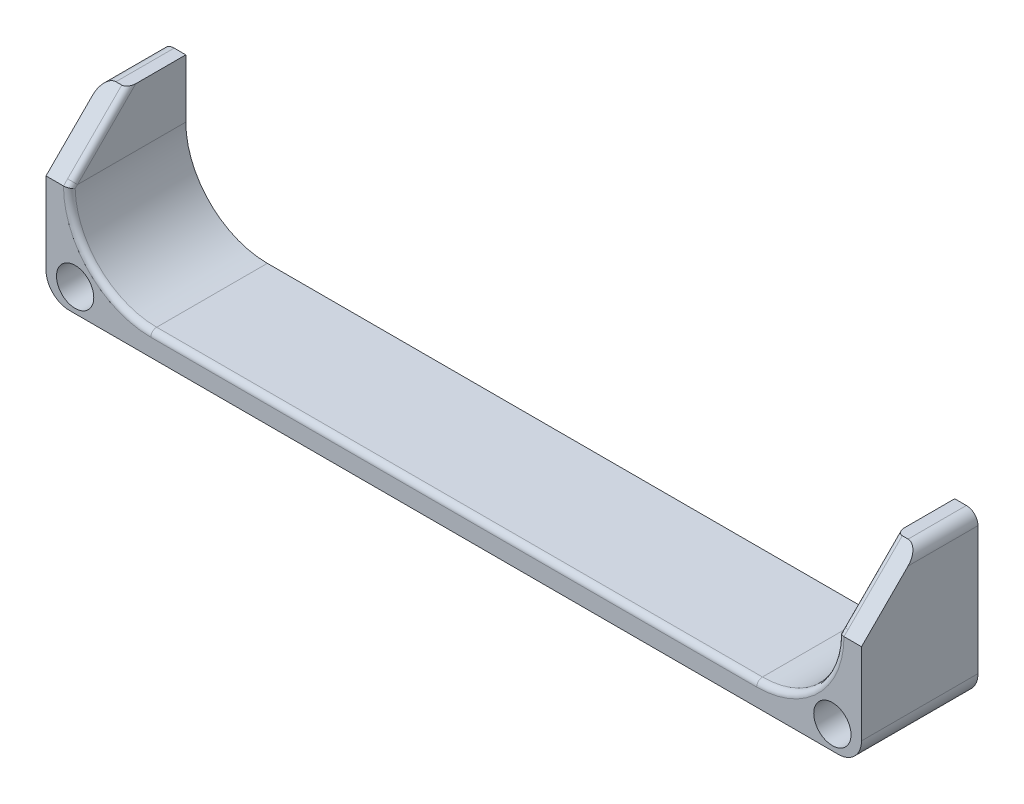
SolidWorks part; units mm, degrees
material "ABS"
ref_plane "Front" through (0, 0, 0) normal (0, 0, 1) x (1, 0, 0)
ref_plane "Top" through (0, 0, 0) normal (0, 1, 0) x (1, 0, 0)
ref_plane "Right" through (0, 0, 0) normal (1, 0, 0) x (0, 0, -1)
sketch "Croquis1" plane through (0, 0, 0) normal (0, 0, 1) x (1, 0, 0)
  line L0 (0, 0) -> (-70, 0)
  line L1 (-70, 0) -> (-70, 28)
  line L2 (-70, 28) -> (-66, 28)
  line L3 (-66, 28) -> (-66, 4)
  line L4 (-66, 4) -> (0, 4)
  line L5 (0, 4) -> (0, 0)
  line L6 (0, 4) -> (0, 31.2012) construction
  dimension "D1" = 140
  dimension "D2" = 4
  dimension "D3" = 4
  dimension "D4" = 28
extrude "Saliente-Extruir1" add sketch "Croquis1" along normal blind 20
fillet "Redondeo1" radius 14 1 edges at (-66, 4, 10)
fillet "Redondeo2" radius 4 1 edges at (-70, 0, 10)
chamfer "Chaflán1" distance 10 angle 45 1 edges at (-68, 28, 20)
sketch "Croquis3" plane through (0, 0, 0) normal (0, 0, 1) x (1, 0, 0)
  line L0 (0, 0) -> (0, 8.7858) construction
  line L1 (-66, 0) -> (0, 0) construction
  circle A0 centre (-65, 4) radius 1.8
  dimension "D1" = 130
  dimension "D2" = 4
  dimension "D3" = 3.6
extrude "Cortar-Extruir1" cut sketch "Croquis3" along normal through all
sketch "Croquis4" plane through (0, 0, 20) normal (0, 0, 1) x (1, 0, 0)
  circle A0 centre (-65, 4) radius 3.2
  dimension "D1" = 6.4
extrude "Cortar-Extruir2" cut sketch "Croquis4" against normal offset from surface (14 mm away) 6 up to face at (-63.2, 4, 0)
fillet "Redondeo3" radius 1 3 edges at (-66, 23, 15) (-61.8995, 8.1005, 20) (-26, 4, 20)
fillet "Redondeo4" radius 2 1 edges at (-70, 28, 5)
mirror "Simetría1" about plane through (0, 4, 20) normal (-1, 0, 0) of bodies 103
